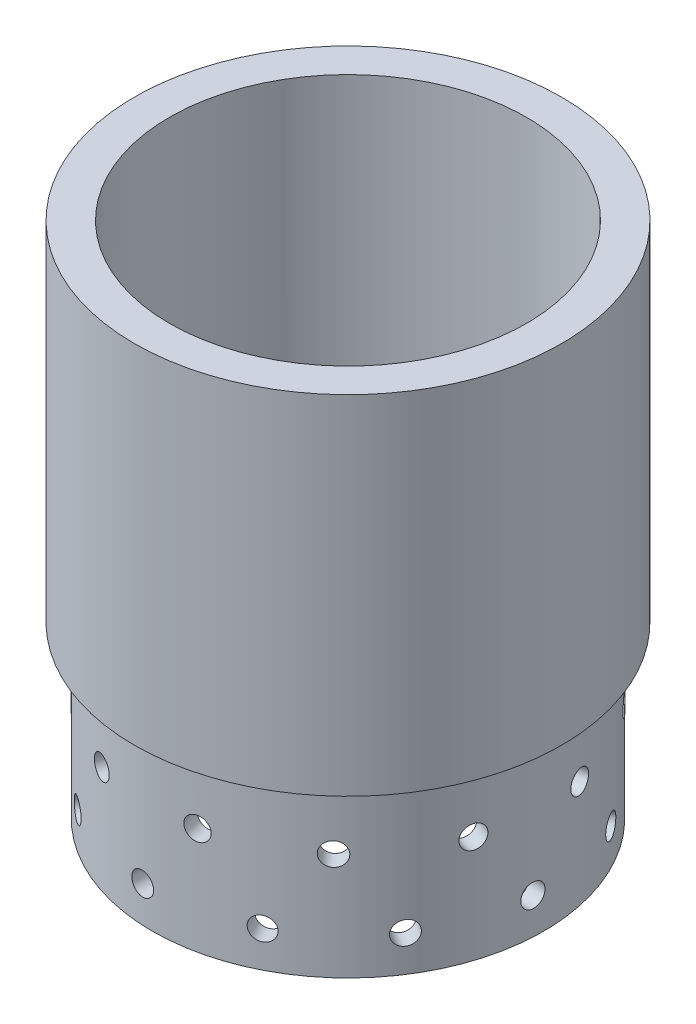
SolidWorks part; units mm, degrees
material "6061-T6 (SS)"
ref_plane "Front Plane" through (0, 0, 0) normal (0, 0, 1) x (1, 0, 0)
ref_plane "Top Plane" through (0, 0, 0) normal (0, 1, 0) x (1, 0, 0)
ref_plane "Right Plane" through (0, 0, 0) normal (1, 0, 0) x (0, 0, -1)
sketch "Sketch1" plane through (0, 0, 0) normal (0, 1, 0) x (1, 0, 0)
  circle A0 centre (0, 0) radius 69.596
  circle A1 centre (0, 0) radius 63.5
  dimension "D1" = 139.192
  dimension "D2" = 127
extrude "Boss-Extrude1" add sketch "Sketch1" along normal blind 57.15
ref_plane "Plane1" through (0, 0, 69.596) normal (0, 0, 1) x (1, 0, 0)
sketch "Sketch2" plane through (0, 0, 69.596) normal (0, 0, 1) x (1, 0, 0)
  circle A0 centre (0, 19.05) radius 3.2639
  dimension "D1" = 6.5278
  dimension "D2" = 19.05
extrude "Cut-Extrude1" [suppressed] cut sketch "Sketch2" against normal up to next
pattern_circular "CirPattern1" [suppressed] count 12 over 360 of bodies 102
ref_plane "Plane2" through (-21.5063, 0, 66.1897) normal (-0.309, 0, 0.9511) x (0, -1, 0)
sketch "Sketch3" plane through (-21.5063, 0, 66.1897) normal (-0.309, 0, 0.9511) x (0, -1, 0)
  line L1 (-57.15, 69.596) -> (-57.15, -69.596) construction
  circle A0 centre (-38.1, 0) radius 4.1021
  dimension "D2" = 8.2042
  dimension "D1" = 19.05
extrude "Cut-Extrude2" cut sketch "Sketch3" against normal up to next
pattern_circular "CirPattern2" count 12 over 360 about axis through (0, 57.15, 0) along (0, -1, 0) of "Cut-Extrude2"
sketch "Sketch4" plane through (0, 57.15, 0) normal (0, 1, 0) x (1, 0, 0)
  circle A0 centre (0, 0) radius 63.5 construction
  circle A1 centre (0, 0) radius 76.073
  circle A3 centre (0, 0) radius 63.5
  dimension "D1" = 152.146
extrude "Boss-Extrude2" [suppressed] add sketch "Sketch4" along normal blind 152.4
sketch "Sketch5" plane through (0, 57.15, 0) normal (0, 1, 0) x (1, 0, 0)
  circle A0 centre (0, 0) radius 63.5 construction
  circle A1 centre (0, 0) radius 63.5
  circle A2 centre (0, 0) radius 75.946
  dimension "D1" = 151.892
extrude "Boss-Extrude3" add sketch "Sketch5" along normal blind 127
other "Move Face1" flip direction yes face at (0, 57.15, 69.596) offset 3.302 parameters "D1"=3.302
ref_plane "Plane3" through (37.9047, 0, -58.3681) normal (0.5446, 0, -0.8387) x (0, -1, 0)
sketch "Sketch7" plane through (37.9047, 0, -58.3681) normal (0.5446, 0, -0.8387) x (0, -1, 0)
  line L0 (-60.452, 0) -> (0, 0) construction
  line L1 (-60.452, -75.946) -> (-60.452, 75.946) construction
  circle A0 centre (-12.827, 0) radius 4.1021
  dimension "D1" = 8.2042
  dimension "D2" = 47.625
extrude "Cut-Extrude3" cut sketch "Sketch7" against normal up to next
pattern_circular "CirPattern3" count 12 over 360 about axis through (0, 57.15, 0) along (0, -1, 0) of "Cut-Extrude3" reverse direction yes
